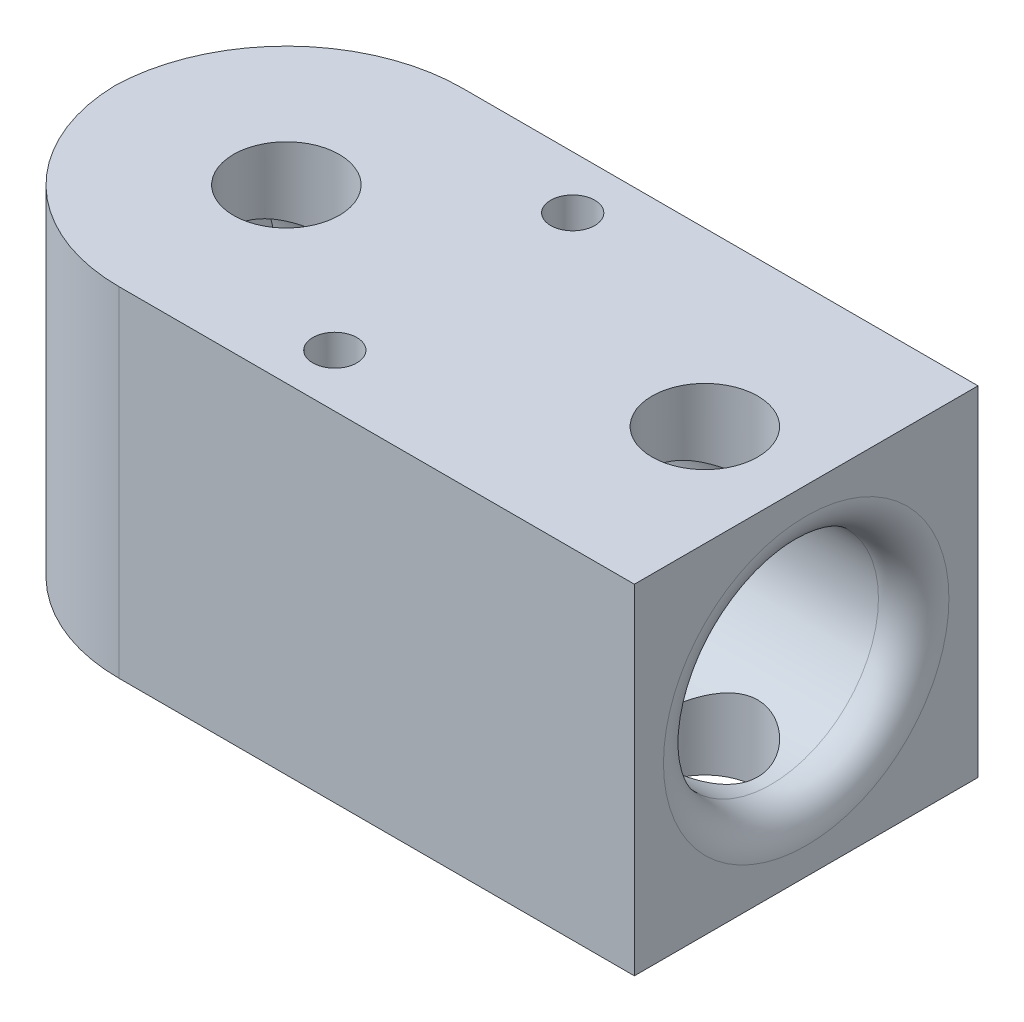
SolidWorks part; units mm, degrees
ref_plane "Front Plane" through (0, 0, 0) normal (0, 0, 1) x (1, 0, 0)
ref_plane "Top Plane" through (0, 0, 0) normal (0, 1, 0) x (1, 0, 0)
ref_plane "Right Plane" through (0, 0, 0) normal (1, 0, 0) x (0, 0, -1)
sketch "Sketch1" plane through (0, 0, 0) normal (0, 1, 0) x (1, 0, 0)
  line L0 (0, -9.75) -> (9.75, -9.75)
  line L1 (0, 0) -> (39.25, 0)
  line L2 (0, 0) -> (0, -19.5)
  line L3 (0, -19.5) -> (39.25, -19.5)
  line L4 (39.25, 0) -> (39.25, -19.5)
  line L5 (19.25, -16.5) -> (19.25, -19.5)
  line L6 (39.25, -16.5) -> (19.25, -16.5)
  line L8 (39.25, -3) -> (19.25, -3)
  line L9 (39.25, -9.75) -> (33.5, -9.75)
  line L10 (19.25, -3) -> (19.25, 0)
  circle A0 centre (19.25, -16.5) radius 1.25
  circle A1 centre (19.25, -3) radius 1.25
  circle A2 centre (9.75, -9.75) radius 3
  circle A3 centre (33.5, -9.75) radius 3
  dimension "D4" = 5.75
  dimension "D8" = 2.5
  dimension "D10" = 2.5
  dimension "D11" = 6
  dimension "D12" = 6
  dimension "D1" = 39.25
  dimension "D2" = 19.5
  dimension "D3" = 9.75
  dimension "D5" = 20
  dimension "D6" = 20
  dimension "D7" = 3
  dimension "D9" = 3
extrude "Boss-Extrude1" add sketch "Sketch1" along normal blind 19.25 contours A3 L4 L8 A1 L10 L1 L2 A2 L3 L5 A0 L6 | A1 L8 L4 L1 L10 | A0 L5 L3 L4 L6 region at (17.4511, 0, 9.75) region at (29.4477, 0, 1.4798) region at (29.4477, 0, 18.0202)
sketch "Sketch2" plane through (39.25, 0, 0) normal (1, 0, 0) x (0, 0, -1)
  line L0 (-19.5, 19.25) -> (0, 0)
  circle A0 centre (-9.75, 9.625) radius 6.1
  dimension "D1" = 12.2
extrude "Cut-Extrude1" cut sketch "Sketch2" against normal blind 36.25 contours L0 A0 | L0 A0 region at (39.25, 11.4674, 7.9312) region at (39.25, 7.7826, 11.5688)
fillet "Fillet1" radius 2 1 edges at (39.25, 9.625, 3.65)
fillet "Fillet3" radius 10 2 edges at (0, 9.625, 19.5) (0, 9.625, 0)
sketch "Sketch4" plane through (3, 0, 0) normal (1, 0, 0) x (0, 0, -1)
  circle A0 centre (-9.75, 9.625) radius 5
extrude "Cut-Extrude3" cut sketch "Sketch4" against normal up to next
